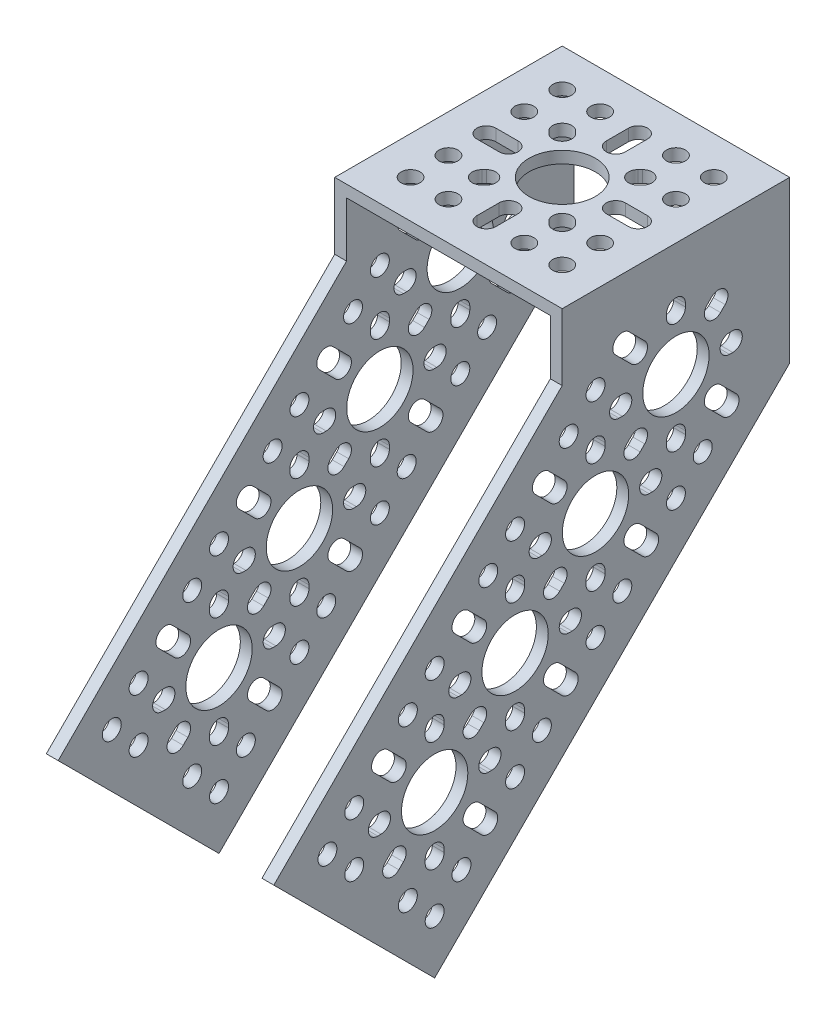
SolidWorks part; units mm, degrees
ref_plane "Front Plane" through (0, 0, 0) normal (0, 0, 1) x (1, 0, 0)
ref_plane "Top Plane" through (0, 0, 0) normal (0, 1, 0) x (1, 0, 0)
ref_plane "Right Plane" through (0, 0, 0) normal (1, 0, 0) x (0, 0, -1)
ref_plane "Plane1" through (21.5, 0, 0) normal (-1, 0, 0) x (0, -1, 0)
sketch "Sketch1" plane through (21.5, 0, 0) normal (-1, 0, 0) x (0, -1, 0)
  line L0 (45.5, -9.9411) -> (11.5589, 24)
  line L1 (11.5589, 24) -> (11.5589, -24)
  line L2 (11.5589, -24) -> (31.4411, -24)
  line L3 (31.4411, -24) -> (45.5, -9.9411)
extrude "Boss-Extrude1" add sketch "Sketch1" against normal blind 2.5
sketch "Sketch2" plane through (0, -11.5589, 0) normal (0, 1, 0) x (-1, 0, 0)
  line L0 (-24, 24) -> (-21.5, 24)
  line L1 (-21.5, 24) -> (-21.5, -24)
  line L2 (-21.5, -24) -> (-24, -24)
  line L3 (-24, -24) -> (-24, 24)
extrude "Boss-Extrude2" add sketch "Sketch2" along normal blind 11.5589
sketch "Sketch3" plane through (0, -17.7794, 17.7794) normal (0, -0.7071, 0.7071) x (1, 0, 0)
  line L0 (21.5, -39.2028) -> (21.5, 8.7972)
  line L1 (21.5, 8.7972) -> (24, 8.7972)
  line L2 (24, 8.7972) -> (24, -39.2028)
  line L3 (24, -39.2028) -> (21.5, -39.2028)
extrude "Boss-Extrude3" add sketch "Sketch3" along normal blind 86.0589
sketch "Sketch4" plane through (0, 0, 0) normal (0, 1, 0) x (-1, 0, 0)
  line L0 (21.5, -24) -> (-24, -24)
  line L1 (-24, -24) -> (-24, 24)
  line L2 (-24, 24) -> (21.5, 24)
  line L3 (21.5, 24) -> (21.5, -24)
extrude "Boss-Extrude4" add sketch "Sketch4" along normal blind 2.5
sketch "Sketch5" plane through (-21.5, 0, 0) normal (-1, 0, 0) x (0, 0, 1)
  line L0 (50.9117, -106.3528) -> (-24, -31.4411)
  line L1 (-24, -31.4411) -> (-24, 2.5)
  line L2 (-24, 2.5) -> (24, 2.5)
  line L3 (24, 2.5) -> (24, -11.5589)
  line L4 (24, -11.5589) -> (84.8528, -72.4117)
  line L5 (84.8528, -72.4117) -> (50.9117, -106.3528)
extrude "Boss-Extrude5" add sketch "Sketch5" along normal blind 2.5
sketch "Sketch6" plane through (-21.5, 0, 0) normal (1, 0, 0) x (0, 0, -1)
  line L0 (-63.6396, -62.5122) -> (-60.3259, -65.8259)
  line L1 (-57.4975, -62.9975) -> (-60.8112, -59.6838)
  arc A0 (-60.8112, -59.6838) -> (-63.6396, -62.5122) centre (-62.2254, -61.098) ccw
  arc A1 (-60.3259, -65.8259) -> (-57.4975, -62.9975) centre (-58.9117, -64.4117) ccw
extrude "Cut-Extrude1" cut sketch "Sketch6" against normal through all
sketch "Sketch7" plane through (-21.5, 0, 0) normal (1, 0, 0) x (0, 0, -1)
  line L0 (-44.3259, -81.8259) -> (-41.0122, -85.1396)
  line L1 (-38.1838, -82.3112) -> (-41.4975, -78.9975)
  arc A0 (-41.0122, -85.1396) -> (-38.1838, -82.3112) centre (-39.598, -83.7254) ccw
  arc A1 (-41.4975, -78.9975) -> (-44.3259, -81.8259) centre (-42.9117, -80.4117) ccw
extrude "Cut-Extrude2" cut sketch "Sketch7" against normal through all
sketch "Sketch8" plane through (-21.5, 0, 0) normal (1, 0, 0) x (0, 0, -1)
  line L0 (-46.669, -45.5416) -> (-43.3553, -48.8553)
  line L1 (-40.5269, -46.0269) -> (-43.8406, -42.7132)
  arc A0 (-43.8406, -42.7132) -> (-46.669, -45.5416) centre (-45.2548, -44.1274) ccw
  arc A1 (-43.3553, -48.8553) -> (-40.5269, -46.0269) centre (-41.9411, -47.4411) ccw
extrude "Cut-Extrude3" cut sketch "Sketch8" against normal through all
sketch "Sketch9" plane through (-21.5, 0, 0) normal (1, 0, 0) x (0, 0, -1)
  line L0 (-27.3553, -64.8553) -> (-24.0416, -68.169)
  line L1 (-21.2132, -65.3406) -> (-24.5269, -62.0269)
  arc A0 (-24.0416, -68.169) -> (-21.2132, -65.3406) centre (-22.6274, -66.7548) ccw
  arc A1 (-24.5269, -62.0269) -> (-27.3553, -64.8553) centre (-25.9411, -63.4411) ccw
extrude "Cut-Extrude4" cut sketch "Sketch9" against normal through all
sketch "Sketch10" plane through (-21.5, 0, 0) normal (1, 0, 0) x (0, 0, -1)
  line L0 (-29.6985, -28.5711) -> (-26.3848, -31.8848)
  line L1 (-23.5563, -29.0563) -> (-26.8701, -25.7426)
  arc A0 (-26.8701, -25.7426) -> (-29.6985, -28.5711) centre (-28.2843, -27.1569) ccw
  arc A1 (-26.3848, -31.8848) -> (-23.5563, -29.0563) centre (-24.9706, -30.4706) ccw
extrude "Cut-Extrude5" cut sketch "Sketch10" against normal through all
sketch "Sketch11" plane through (-21.5, 0, 0) normal (1, 0, 0) x (0, 0, -1)
  line L0 (-10.3848, -47.8848) -> (-7.0711, -51.1985)
  line L1 (-4.2426, -48.3701) -> (-7.5563, -45.0563)
  arc A0 (-7.0711, -51.1985) -> (-4.2426, -48.3701) centre (-5.6569, -49.7843) ccw
  arc A1 (-7.5563, -45.0563) -> (-10.3848, -47.8848) centre (-8.9706, -46.4706) ccw
extrude "Cut-Extrude6" cut sketch "Sketch11" against normal through all
sketch "Sketch12" plane through (-21.5, 0, 0) normal (1, 0, 0) x (0, 0, -1)
  line L0 (-12.7279, -11.6005) -> (-9.4142, -14.9142)
  line L1 (-6.5858, -12.0858) -> (-9.8995, -8.7721)
  arc A0 (-9.8995, -8.7721) -> (-12.7279, -11.6005) centre (-11.3137, -10.1863) ccw
  arc A1 (-9.4142, -14.9142) -> (-6.5858, -12.0858) centre (-8, -13.5) ccw
extrude "Cut-Extrude7" cut sketch "Sketch12" against normal through all
sketch "Sketch13" plane through (-21.5, 0, 0) normal (1, 0, 0) x (0, 0, -1)
  line L0 (6.5858, -30.9142) -> (9.8995, -34.2279)
  line L1 (12.7279, -31.3995) -> (9.4142, -28.0858)
  arc A0 (9.8995, -34.2279) -> (12.7279, -31.3995) centre (11.3137, -32.8137) ccw
  arc A1 (9.4142, -28.0858) -> (6.5858, -30.9142) centre (8, -29.5) ccw
extrude "Cut-Extrude8" cut sketch "Sketch13" against normal through all
sketch "Sketch14" plane through (-21.5, 0, 0) normal (1, 0, 0) x (0, 0, -1)
  line L0 (-58.468, -82.7965) -> (-57.4975, -81.8259)
  line L1 (-60.3259, -78.9975) -> (-61.2965, -79.968)
  arc A0 (-57.4975, -81.8259) -> (-60.3259, -78.9975) centre (-58.9117, -80.4117) ccw
  arc A1 (-61.2965, -79.968) -> (-58.468, -82.7965) centre (-59.8823, -81.3823) ccw
extrude "Cut-Extrude9" cut sketch "Sketch14" against normal through all
sketch "Sketch15" plane through (-21.5, 0, 0) normal (1, 0, 0) x (0, 0, -1)
  line L0 (-41.4975, -65.8259) -> (-40.5269, -64.8553)
  line L1 (-43.3553, -62.0269) -> (-44.3259, -62.9975)
  arc A0 (-40.5269, -64.8553) -> (-43.3553, -62.0269) centre (-41.9411, -63.4411) ccw
  arc A1 (-44.3259, -62.9975) -> (-41.4975, -65.8259) centre (-42.9117, -64.4117) ccw
extrude "Cut-Extrude10" cut sketch "Sketch15" against normal through all
sketch "Sketch16" plane through (-21.5, 0, 0) normal (1, 0, 0) x (0, 0, -1)
  line L0 (-24.5269, -48.8553) -> (-23.5563, -47.8848)
  line L1 (-26.3848, -45.0563) -> (-27.3553, -46.0269)
  arc A0 (-23.5563, -47.8848) -> (-26.3848, -45.0563) centre (-24.9706, -46.4706) ccw
  arc A1 (-27.3553, -46.0269) -> (-24.5269, -48.8553) centre (-25.9411, -47.4411) ccw
extrude "Cut-Extrude11" cut sketch "Sketch16" against normal through all
sketch "Sketch17" plane through (-21.5, 0, 0) normal (1, 0, 0) x (0, 0, -1)
  line L0 (-7.5563, -31.8848) -> (-6.5858, -30.9142)
  line L1 (-9.4142, -28.0858) -> (-10.3848, -29.0563)
  arc A0 (-6.5858, -30.9142) -> (-9.4142, -28.0858) centre (-8, -29.5) ccw
  arc A1 (-10.3848, -29.0563) -> (-7.5563, -31.8848) centre (-8.9706, -30.4706) ccw
extrude "Cut-Extrude12" cut sketch "Sketch17" against normal through all
sketch "Sketch18" plane through (-21.5, 0, 0) normal (1, 0, 0) x (0, 0, -1)
  line L0 (7.5563, -11.1152) -> (6.5858, -12.0858)
  line L1 (9.4142, -14.9142) -> (10.3848, -13.9437)
  arc A0 (6.5858, -12.0858) -> (9.4142, -14.9142) centre (8, -13.5) ccw
  arc A1 (10.3848, -13.9437) -> (7.5563, -11.1152) centre (8.9706, -12.5294) ccw
extrude "Cut-Extrude13" cut sketch "Sketch18" against normal through all
sketch "Sketch19" plane through (-21.5, 0, 0) normal (1, 0, 0) x (0, 0, -1)
  line L0 (-48.9117, -61.098) -> (-48.9117, -60.4117)
  line L1 (-52.9117, -60.4117) -> (-52.9117, -61.098)
  arc A0 (-48.9117, -60.4117) -> (-52.9117, -60.4117) centre (-50.9117, -60.4117) ccw
  arc A1 (-52.9117, -61.098) -> (-48.9117, -61.098) centre (-50.9117, -61.098) ccw
extrude "Cut-Extrude14" cut sketch "Sketch19" against normal through all
sketch "Sketch20" plane through (-21.5, 0, 0) normal (1, 0, 0) x (0, 0, -1)
  line L0 (-39.598, -74.4117) -> (-38.9117, -74.4117)
  line L1 (-38.9117, -70.4117) -> (-39.598, -70.4117)
  arc A0 (-38.9117, -74.4117) -> (-38.9117, -70.4117) centre (-38.9117, -72.4117) ccw
  arc A1 (-39.598, -70.4117) -> (-39.598, -74.4117) centre (-39.598, -72.4117) ccw
extrude "Cut-Extrude15" cut sketch "Sketch20" against normal through all
sketch "Sketch21" plane through (-21.5, 0, 0) normal (1, 0, 0) x (0, 0, -1)
  line L0 (-52.9117, -83.7254) -> (-52.9117, -84.4117)
  line L1 (-48.9117, -84.4117) -> (-48.9117, -83.7254)
  arc A0 (-52.9117, -84.4117) -> (-48.9117, -84.4117) centre (-50.9117, -84.4117) ccw
  arc A1 (-48.9117, -83.7254) -> (-52.9117, -83.7254) centre (-50.9117, -83.7254) ccw
extrude "Cut-Extrude16" cut sketch "Sketch21" against normal through all
sketch "Sketch22" plane through (-21.5, 0, 0) normal (1, 0, 0) x (0, 0, -1)
  line L0 (-62.9117, -74.4117) -> (-62.2254, -74.4117)
  line L1 (-62.2254, -70.4117) -> (-62.9117, -70.4117)
  arc A0 (-62.9117, -70.4117) -> (-62.9117, -74.4117) centre (-62.9117, -72.4117) ccw
  arc A1 (-62.2254, -74.4117) -> (-62.2254, -70.4117) centre (-62.2254, -72.4117) ccw
extrude "Cut-Extrude17" cut sketch "Sketch22" against normal through all
sketch "Sketch23" plane through (-21.5, 0, 0) normal (1, 0, 0) x (0, 0, -1)
  line L0 (-31.9411, -44.1274) -> (-31.9411, -43.4411)
  line L1 (-35.9411, -43.4411) -> (-35.9411, -44.1274)
  arc A0 (-31.9411, -43.4411) -> (-35.9411, -43.4411) centre (-33.9411, -43.4411) ccw
  arc A1 (-35.9411, -44.1274) -> (-31.9411, -44.1274) centre (-33.9411, -44.1274) ccw
extrude "Cut-Extrude18" cut sketch "Sketch23" against normal through all
sketch "Sketch24" plane through (-21.5, 0, 0) normal (1, 0, 0) x (0, 0, -1)
  line L0 (-22.6274, -57.4411) -> (-21.9411, -57.4411)
  line L1 (-21.9411, -53.4411) -> (-22.6274, -53.4411)
  arc A0 (-21.9411, -57.4411) -> (-21.9411, -53.4411) centre (-21.9411, -55.4411) ccw
  arc A1 (-22.6274, -53.4411) -> (-22.6274, -57.4411) centre (-22.6274, -55.4411) ccw
extrude "Cut-Extrude19" cut sketch "Sketch24" against normal through all
sketch "Sketch25" plane through (-21.5, 0, 0) normal (1, 0, 0) x (0, 0, -1)
  line L0 (-35.9411, -66.7548) -> (-35.9411, -67.4411)
  line L1 (-31.9411, -67.4411) -> (-31.9411, -66.7548)
  arc A0 (-35.9411, -67.4411) -> (-31.9411, -67.4411) centre (-33.9411, -67.4411) ccw
  arc A1 (-31.9411, -66.7548) -> (-35.9411, -66.7548) centre (-33.9411, -66.7548) ccw
extrude "Cut-Extrude20" cut sketch "Sketch25" against normal through all
sketch "Sketch26" plane through (-21.5, 0, 0) normal (1, 0, 0) x (0, 0, -1)
  line L0 (-45.9411, -57.4411) -> (-45.2548, -57.4411)
  line L1 (-45.2548, -53.4411) -> (-45.9411, -53.4411)
  arc A0 (-45.9411, -53.4411) -> (-45.9411, -57.4411) centre (-45.9411, -55.4411) ccw
  arc A1 (-45.2548, -57.4411) -> (-45.2548, -53.4411) centre (-45.2548, -55.4411) ccw
extrude "Cut-Extrude21" cut sketch "Sketch26" against normal through all
sketch "Sketch27" plane through (-21.5, 0, 0) normal (1, 0, 0) x (0, 0, -1)
  line L0 (-14.9706, -27.1569) -> (-14.9706, -26.4706)
  line L1 (-18.9706, -26.4706) -> (-18.9706, -27.1569)
  arc A0 (-14.9706, -26.4706) -> (-18.9706, -26.4706) centre (-16.9706, -26.4706) ccw
  arc A1 (-18.9706, -27.1569) -> (-14.9706, -27.1569) centre (-16.9706, -27.1569) ccw
extrude "Cut-Extrude22" cut sketch "Sketch27" against normal through all
sketch "Sketch28" plane through (-21.5, 0, 0) normal (1, 0, 0) x (0, 0, -1)
  line L0 (-5.6569, -40.4706) -> (-4.9706, -40.4706)
  line L1 (-4.9706, -36.4706) -> (-5.6569, -36.4706)
  arc A0 (-4.9706, -40.4706) -> (-4.9706, -36.4706) centre (-4.9706, -38.4706) ccw
  arc A1 (-5.6569, -36.4706) -> (-5.6569, -40.4706) centre (-5.6569, -38.4706) ccw
extrude "Cut-Extrude23" cut sketch "Sketch28" against normal through all
sketch "Sketch29" plane through (-21.5, 0, 0) normal (1, 0, 0) x (0, 0, -1)
  line L0 (-18.9706, -49.7843) -> (-18.9706, -50.4706)
  line L1 (-14.9706, -50.4706) -> (-14.9706, -49.7843)
  arc A0 (-18.9706, -50.4706) -> (-14.9706, -50.4706) centre (-16.9706, -50.4706) ccw
  arc A1 (-14.9706, -49.7843) -> (-18.9706, -49.7843) centre (-16.9706, -49.7843) ccw
extrude "Cut-Extrude24" cut sketch "Sketch29" against normal through all
sketch "Sketch30" plane through (-21.5, 0, 0) normal (1, 0, 0) x (0, 0, -1)
  line L0 (-28.9706, -40.4706) -> (-28.2843, -40.4706)
  line L1 (-28.2843, -36.4706) -> (-28.9706, -36.4706)
  arc A0 (-28.9706, -36.4706) -> (-28.9706, -40.4706) centre (-28.9706, -38.4706) ccw
  arc A1 (-28.2843, -40.4706) -> (-28.2843, -36.4706) centre (-28.2843, -38.4706) ccw
extrude "Cut-Extrude25" cut sketch "Sketch30" against normal through all
sketch "Sketch31" plane through (-21.5, 0, 0) normal (1, 0, 0) x (0, 0, -1)
  line L0 (2, -10.1863) -> (2, -9.5)
  line L1 (-2, -9.5) -> (-2, -10.1863)
  arc A0 (2, -9.5) -> (-2, -9.5) centre (0, -9.5) ccw
  arc A1 (-2, -10.1863) -> (2, -10.1863) centre (0, -10.1863) ccw
extrude "Cut-Extrude26" cut sketch "Sketch31" against normal through all
sketch "Sketch32" plane through (-21.5, 0, 0) normal (1, 0, 0) x (0, 0, -1)
  line L0 (11.3137, -23.5) -> (12, -23.5)
  line L1 (12, -19.5) -> (11.3137, -19.5)
  arc A0 (12, -23.5) -> (12, -19.5) centre (12, -21.5) ccw
  arc A1 (11.3137, -19.5) -> (11.3137, -23.5) centre (11.3137, -21.5) ccw
extrude "Cut-Extrude27" cut sketch "Sketch32" against normal through all
sketch "Sketch33" plane through (-21.5, 0, 0) normal (1, 0, 0) x (0, 0, -1)
  line L0 (-2, -32.8137) -> (-2, -33.5)
  line L1 (2, -33.5) -> (2, -32.8137)
  arc A0 (-2, -33.5) -> (2, -33.5) centre (0, -33.5) ccw
  arc A1 (2, -32.8137) -> (-2, -32.8137) centre (0, -32.8137) ccw
extrude "Cut-Extrude28" cut sketch "Sketch33" against normal through all
sketch "Sketch34" plane through (0, 2.5, 0) normal (0, 1, 0) x (-1, 0, 0)
  line L0 (-2, -11.3137) -> (-2, -16)
  line L1 (2, -16) -> (2, -11.3137)
  arc A0 (-2, -16) -> (2, -16) centre (0, -16) ccw
  arc A1 (2, -11.3137) -> (-2, -11.3137) centre (0, -11.3137) ccw
extrude "Cut-Extrude29" cut sketch "Sketch34" against normal through all
sketch "Sketch35" plane through (0, 2.5, 0) normal (0, 1, 0) x (-1, 0, 0)
  line L0 (11.3137, -2) -> (16, -2)
  line L1 (16, 2) -> (11.3137, 2)
  arc A0 (16, -2) -> (16, 2) centre (16, 0) ccw
  arc A1 (11.3137, 2) -> (11.3137, -2) centre (11.3137, 0) ccw
extrude "Cut-Extrude30" cut sketch "Sketch35" against normal through all
sketch "Sketch36" plane through (0, 2.5, 0) normal (0, 1, 0) x (-1, 0, 0)
  line L0 (2, 11.3137) -> (2, 16)
  line L1 (-2, 16) -> (-2, 11.3137)
  arc A0 (2, 16) -> (-2, 16) centre (0, 16) ccw
  arc A1 (-2, 11.3137) -> (2, 11.3137) centre (0, 11.3137) ccw
extrude "Cut-Extrude31" cut sketch "Sketch36" against normal through all
sketch "Sketch37" plane through (0, 2.5, 0) normal (0, 1, 0) x (-1, 0, 0)
  line L0 (-11.3137, 2) -> (-16, 2)
  line L1 (-16, -2) -> (-11.3137, -2)
  arc A0 (-16, 2) -> (-16, -2) centre (-16, 0) ccw
  arc A1 (-11.3137, -2) -> (-11.3137, 2) centre (-11.3137, 0) ccw
extrude "Cut-Extrude32" cut sketch "Sketch37" against normal through all
sketch "Sketch38" plane through (0, 2.5, 0) normal (0, 1, 0) x (-1, 0, 0)
  line L0 (-7.0711, -9.8995) -> (-6.5858, -9.4142)
  line L1 (-9.4142, -6.5858) -> (-9.8995, -7.0711)
  arc A0 (-9.8995, -7.0711) -> (-7.0711, -9.8995) centre (-8.4853, -8.4853) ccw
  arc A1 (-6.5858, -9.4142) -> (-9.4142, -6.5858) centre (-8, -8) ccw
extrude "Cut-Extrude33" cut sketch "Sketch38" against normal through all
sketch "Sketch39" plane through (0, 2.5, 0) normal (0, 1, 0) x (-1, 0, 0)
  line L0 (6.5858, -9.4142) -> (7.0711, -9.8995)
  line L1 (9.8995, -7.0711) -> (9.4142, -6.5858)
  arc A0 (7.0711, -9.8995) -> (9.8995, -7.0711) centre (8.4853, -8.4853) ccw
  arc A1 (9.4142, -6.5858) -> (6.5858, -9.4142) centre (8, -8) ccw
extrude "Cut-Extrude34" cut sketch "Sketch39" against normal through all
sketch "Sketch40" plane through (0, 2.5, 0) normal (0, 1, 0) x (-1, 0, 0)
  line L0 (9.4142, 6.5858) -> (9.8995, 7.0711)
  line L1 (7.0711, 9.8995) -> (6.5858, 9.4142)
  arc A0 (9.8995, 7.0711) -> (7.0711, 9.8995) centre (8.4853, 8.4853) ccw
  arc A1 (6.5858, 9.4142) -> (9.4142, 6.5858) centre (8, 8) ccw
extrude "Cut-Extrude35" cut sketch "Sketch40" against normal through all
sketch "Sketch41" plane through (24, 0, 0) normal (1, 0, 0) x (0, 0, -1)
  line L0 (-63.6396, -62.5122) -> (-60.3259, -65.8259)
  line L1 (-57.4975, -62.9975) -> (-60.8112, -59.6838)
  arc A0 (-60.8112, -59.6838) -> (-63.6396, -62.5122) centre (-62.2254, -61.098) ccw
  arc A1 (-60.3259, -65.8259) -> (-57.4975, -62.9975) centre (-58.9117, -64.4117) ccw
extrude "Cut-Extrude36" cut sketch "Sketch41" against normal up to next
sketch "Sketch42" plane through (24, 0, 0) normal (1, 0, 0) x (0, 0, -1)
  line L0 (-44.3259, -81.8259) -> (-41.0122, -85.1396)
  line L1 (-38.1838, -82.3112) -> (-41.4975, -78.9975)
  arc A0 (-41.0122, -85.1396) -> (-38.1838, -82.3112) centre (-39.598, -83.7254) ccw
  arc A1 (-41.4975, -78.9975) -> (-44.3259, -81.8259) centre (-42.9117, -80.4117) ccw
extrude "Cut-Extrude37" cut sketch "Sketch42" against normal up to next
sketch "Sketch43" plane through (24, 0, 0) normal (1, 0, 0) x (0, 0, -1)
  line L0 (-46.669, -45.5416) -> (-43.3553, -48.8553)
  line L1 (-40.5269, -46.0269) -> (-43.8406, -42.7132)
  arc A0 (-43.8406, -42.7132) -> (-46.669, -45.5416) centre (-45.2548, -44.1274) ccw
  arc A1 (-43.3553, -48.8553) -> (-40.5269, -46.0269) centre (-41.9411, -47.4411) ccw
extrude "Cut-Extrude38" cut sketch "Sketch43" against normal up to next
sketch "Sketch44" plane through (24, 0, 0) normal (1, 0, 0) x (0, 0, -1)
  line L0 (-27.3553, -64.8553) -> (-24.0416, -68.169)
  line L1 (-21.2132, -65.3406) -> (-24.5269, -62.0269)
  arc A0 (-24.0416, -68.169) -> (-21.2132, -65.3406) centre (-22.6274, -66.7548) ccw
  arc A1 (-24.5269, -62.0269) -> (-27.3553, -64.8553) centre (-25.9411, -63.4411) ccw
extrude "Cut-Extrude39" cut sketch "Sketch44" against normal up to next
sketch "Sketch45" plane through (24, 0, 0) normal (1, 0, 0) x (0, 0, -1)
  line L0 (-29.6985, -28.5711) -> (-26.3848, -31.8848)
  line L1 (-23.5563, -29.0563) -> (-26.8701, -25.7426)
  arc A0 (-26.8701, -25.7426) -> (-29.6985, -28.5711) centre (-28.2843, -27.1569) ccw
  arc A1 (-26.3848, -31.8848) -> (-23.5563, -29.0563) centre (-24.9706, -30.4706) ccw
extrude "Cut-Extrude40" cut sketch "Sketch45" against normal up to next
sketch "Sketch46" plane through (24, 0, 0) normal (1, 0, 0) x (0, 0, -1)
  line L0 (-10.3848, -47.8848) -> (-7.0711, -51.1985)
  line L1 (-4.2426, -48.3701) -> (-7.5563, -45.0563)
  arc A0 (-7.0711, -51.1985) -> (-4.2426, -48.3701) centre (-5.6569, -49.7843) ccw
  arc A1 (-7.5563, -45.0563) -> (-10.3848, -47.8848) centre (-8.9706, -46.4706) ccw
extrude "Cut-Extrude41" cut sketch "Sketch46" against normal up to next
sketch "Sketch47" plane through (24, 0, 0) normal (1, 0, 0) x (0, 0, -1)
  line L0 (-12.7279, -11.6005) -> (-9.4142, -14.9142)
  line L1 (-6.5858, -12.0858) -> (-9.8995, -8.7721)
  arc A0 (-9.8995, -8.7721) -> (-12.7279, -11.6005) centre (-11.3137, -10.1863) ccw
  arc A1 (-9.4142, -14.9142) -> (-6.5858, -12.0858) centre (-8, -13.5) ccw
extrude "Cut-Extrude42" cut sketch "Sketch47" against normal up to next
sketch "Sketch48" plane through (24, 0, 0) normal (1, 0, 0) x (0, 0, -1)
  line L0 (6.5858, -30.9142) -> (9.8995, -34.2279)
  line L1 (12.7279, -31.3995) -> (9.4142, -28.0858)
  arc A0 (9.8995, -34.2279) -> (12.7279, -31.3995) centre (11.3137, -32.8137) ccw
  arc A1 (9.4142, -28.0858) -> (6.5858, -30.9142) centre (8, -29.5) ccw
extrude "Cut-Extrude43" cut sketch "Sketch48" against normal up to next
sketch "Sketch49" plane through (24, 0, 0) normal (1, 0, 0) x (0, 0, -1)
  line L0 (-58.468, -82.7965) -> (-57.4975, -81.8259)
  line L1 (-60.3259, -78.9975) -> (-61.2965, -79.968)
  arc A0 (-57.4975, -81.8259) -> (-60.3259, -78.9975) centre (-58.9117, -80.4117) ccw
  arc A1 (-61.2965, -79.968) -> (-58.468, -82.7965) centre (-59.8823, -81.3823) ccw
extrude "Cut-Extrude44" cut sketch "Sketch49" against normal through all
sketch "Sketch50" plane through (24, 0, 0) normal (1, 0, 0) x (0, 0, -1)
  line L0 (-41.4975, -65.8259) -> (-40.5269, -64.8553)
  line L1 (-43.3553, -62.0269) -> (-44.3259, -62.9975)
  arc A0 (-40.5269, -64.8553) -> (-43.3553, -62.0269) centre (-41.9411, -63.4411) ccw
  arc A1 (-44.3259, -62.9975) -> (-41.4975, -65.8259) centre (-42.9117, -64.4117) ccw
extrude "Cut-Extrude45" cut sketch "Sketch50" against normal through all
sketch "Sketch51" plane through (24, 0, 0) normal (1, 0, 0) x (0, 0, -1)
  line L0 (-24.5269, -48.8553) -> (-23.5563, -47.8848)
  line L1 (-26.3848, -45.0563) -> (-27.3553, -46.0269)
  arc A0 (-23.5563, -47.8848) -> (-26.3848, -45.0563) centre (-24.9706, -46.4706) ccw
  arc A1 (-27.3553, -46.0269) -> (-24.5269, -48.8553) centre (-25.9411, -47.4411) ccw
extrude "Cut-Extrude46" cut sketch "Sketch51" against normal through all
sketch "Sketch52" plane through (24, 0, 0) normal (1, 0, 0) x (0, 0, -1)
  line L0 (-7.5563, -31.8848) -> (-6.5858, -30.9142)
  line L1 (-9.4142, -28.0858) -> (-10.3848, -29.0563)
  arc A0 (-6.5858, -30.9142) -> (-9.4142, -28.0858) centre (-8, -29.5) ccw
  arc A1 (-10.3848, -29.0563) -> (-7.5563, -31.8848) centre (-8.9706, -30.4706) ccw
extrude "Cut-Extrude47" cut sketch "Sketch52" against normal through all
sketch "Sketch53" plane through (24, 0, 0) normal (1, 0, 0) x (0, 0, -1)
  line L0 (7.5563, -11.1152) -> (6.5858, -12.0858)
  line L1 (9.4142, -14.9142) -> (10.3848, -13.9437)
  arc A0 (6.5858, -12.0858) -> (9.4142, -14.9142) centre (8, -13.5) ccw
  arc A1 (10.3848, -13.9437) -> (7.5563, -11.1152) centre (8.9706, -12.5294) ccw
extrude "Cut-Extrude48" cut sketch "Sketch53" against normal through all
sketch "Sketch54" plane through (24, 0, 0) normal (1, 0, 0) x (0, 0, -1)
  line L0 (-48.9117, -61.098) -> (-48.9117, -60.4117)
  line L1 (-52.9117, -60.4117) -> (-52.9117, -61.098)
  arc A0 (-48.9117, -60.4117) -> (-52.9117, -60.4117) centre (-50.9117, -60.4117) ccw
  arc A1 (-52.9117, -61.098) -> (-48.9117, -61.098) centre (-50.9117, -61.098) ccw
extrude "Cut-Extrude49" cut sketch "Sketch54" against normal through all
sketch "Sketch55" plane through (24, 0, 0) normal (1, 0, 0) x (0, 0, -1)
  line L0 (-39.598, -74.4117) -> (-38.9117, -74.4117)
  line L1 (-38.9117, -70.4117) -> (-39.598, -70.4117)
  arc A0 (-38.9117, -74.4117) -> (-38.9117, -70.4117) centre (-38.9117, -72.4117) ccw
  arc A1 (-39.598, -70.4117) -> (-39.598, -74.4117) centre (-39.598, -72.4117) ccw
extrude "Cut-Extrude50" cut sketch "Sketch55" against normal through all
sketch "Sketch56" plane through (24, 0, 0) normal (1, 0, 0) x (0, 0, -1)
  line L0 (-52.9117, -83.7254) -> (-52.9117, -84.4117)
  line L1 (-48.9117, -84.4117) -> (-48.9117, -83.7254)
  arc A0 (-52.9117, -84.4117) -> (-48.9117, -84.4117) centre (-50.9117, -84.4117) ccw
  arc A1 (-48.9117, -83.7254) -> (-52.9117, -83.7254) centre (-50.9117, -83.7254) ccw
extrude "Cut-Extrude51" cut sketch "Sketch56" against normal through all
sketch "Sketch57" plane through (24, 0, 0) normal (1, 0, 0) x (0, 0, -1)
  line L0 (-62.2254, -70.4117) -> (-62.9117, -70.4117)
  line L1 (-62.9117, -74.4117) -> (-62.2254, -74.4117)
  arc A0 (-62.9117, -70.4117) -> (-62.9117, -74.4117) centre (-62.9117, -72.4117) ccw
  arc A1 (-62.2254, -74.4117) -> (-62.2254, -70.4117) centre (-62.2254, -72.4117) ccw
extrude "Cut-Extrude52" cut sketch "Sketch57" against normal through all
sketch "Sketch58" plane through (24, 0, 0) normal (1, 0, 0) x (0, 0, -1)
  line L0 (-31.9411, -44.1274) -> (-31.9411, -43.4411)
  line L1 (-35.9411, -43.4411) -> (-35.9411, -44.1274)
  arc A0 (-31.9411, -43.4411) -> (-35.9411, -43.4411) centre (-33.9411, -43.4411) ccw
  arc A1 (-35.9411, -44.1274) -> (-31.9411, -44.1274) centre (-33.9411, -44.1274) ccw
extrude "Cut-Extrude53" cut sketch "Sketch58" against normal through all
sketch "Sketch59" plane through (24, 0, 0) normal (1, 0, 0) x (0, 0, -1)
  line L0 (-22.6274, -57.4411) -> (-21.9411, -57.4411)
  line L1 (-21.9411, -53.4411) -> (-22.6274, -53.4411)
  arc A0 (-21.9411, -57.4411) -> (-21.9411, -53.4411) centre (-21.9411, -55.4411) ccw
  arc A1 (-22.6274, -53.4411) -> (-22.6274, -57.4411) centre (-22.6274, -55.4411) ccw
extrude "Cut-Extrude54" cut sketch "Sketch59" against normal through all
sketch "Sketch60" plane through (24, 0, 0) normal (1, 0, 0) x (0, 0, -1)
  line L0 (-35.9411, -66.7548) -> (-35.9411, -67.4411)
  line L1 (-31.9411, -67.4411) -> (-31.9411, -66.7548)
  arc A0 (-35.9411, -67.4411) -> (-31.9411, -67.4411) centre (-33.9411, -67.4411) ccw
  arc A1 (-31.9411, -66.7548) -> (-35.9411, -66.7548) centre (-33.9411, -66.7548) ccw
extrude "Cut-Extrude55" cut sketch "Sketch60" against normal through all
sketch "Sketch61" plane through (24, 0, 0) normal (1, 0, 0) x (0, 0, -1)
  line L0 (-45.2548, -53.4411) -> (-45.9411, -53.4411)
  line L1 (-45.9411, -57.4411) -> (-45.2548, -57.4411)
  arc A0 (-45.9411, -53.4411) -> (-45.9411, -57.4411) centre (-45.9411, -55.4411) ccw
  arc A1 (-45.2548, -57.4411) -> (-45.2548, -53.4411) centre (-45.2548, -55.4411) ccw
extrude "Cut-Extrude56" cut sketch "Sketch61" against normal through all
sketch "Sketch62" plane through (24, 0, 0) normal (1, 0, 0) x (0, 0, -1)
  line L0 (-14.9706, -27.1569) -> (-14.9706, -26.4706)
  line L1 (-18.9706, -26.4706) -> (-18.9706, -27.1569)
  arc A0 (-14.9706, -26.4706) -> (-18.9706, -26.4706) centre (-16.9706, -26.4706) ccw
  arc A1 (-18.9706, -27.1569) -> (-14.9706, -27.1569) centre (-16.9706, -27.1569) ccw
extrude "Cut-Extrude57" cut sketch "Sketch62" against normal through all
sketch "Sketch63" plane through (24, 0, 0) normal (1, 0, 0) x (0, 0, -1)
  line L0 (-5.6569, -40.4706) -> (-4.9706, -40.4706)
  line L1 (-4.9706, -36.4706) -> (-5.6569, -36.4706)
  arc A0 (-4.9706, -40.4706) -> (-4.9706, -36.4706) centre (-4.9706, -38.4706) ccw
  arc A1 (-5.6569, -36.4706) -> (-5.6569, -40.4706) centre (-5.6569, -38.4706) ccw
extrude "Cut-Extrude58" cut sketch "Sketch63" against normal through all
sketch "Sketch64" plane through (24, 0, 0) normal (1, 0, 0) x (0, 0, -1)
  line L0 (-18.9706, -49.7843) -> (-18.9706, -50.4706)
  line L1 (-14.9706, -50.4706) -> (-14.9706, -49.7843)
  arc A0 (-18.9706, -50.4706) -> (-14.9706, -50.4706) centre (-16.9706, -50.4706) ccw
  arc A1 (-14.9706, -49.7843) -> (-18.9706, -49.7843) centre (-16.9706, -49.7843) ccw
extrude "Cut-Extrude59" cut sketch "Sketch64" against normal through all
sketch "Sketch65" plane through (24, 0, 0) normal (1, 0, 0) x (0, 0, -1)
  line L0 (-28.2843, -36.4706) -> (-28.9706, -36.4706)
  line L1 (-28.9706, -40.4706) -> (-28.2843, -40.4706)
  arc A0 (-28.9706, -36.4706) -> (-28.9706, -40.4706) centre (-28.9706, -38.4706) ccw
  arc A1 (-28.2843, -40.4706) -> (-28.2843, -36.4706) centre (-28.2843, -38.4706) ccw
extrude "Cut-Extrude60" cut sketch "Sketch65" against normal through all
sketch "Sketch66" plane through (24, 0, 0) normal (1, 0, 0) x (0, 0, -1)
  line L0 (2, -10.1863) -> (2, -9.5)
  line L1 (-2, -9.5) -> (-2, -10.1863)
  arc A0 (2, -9.5) -> (-2, -9.5) centre (0, -9.5) ccw
  arc A1 (-2, -10.1863) -> (2, -10.1863) centre (0, -10.1863) ccw
extrude "Cut-Extrude61" cut sketch "Sketch66" against normal through all
sketch "Sketch67" plane through (24, 0, 0) normal (1, 0, 0) x (0, 0, -1)
  line L0 (11.3137, -23.5) -> (12, -23.5)
  line L1 (12, -19.5) -> (11.3137, -19.5)
  arc A0 (12, -23.5) -> (12, -19.5) centre (12, -21.5) ccw
  arc A1 (11.3137, -19.5) -> (11.3137, -23.5) centre (11.3137, -21.5) ccw
extrude "Cut-Extrude62" cut sketch "Sketch67" against normal through all
sketch "Sketch68" plane through (24, 0, 0) normal (1, 0, 0) x (0, 0, -1)
  line L0 (-2, -32.8137) -> (-2, -33.5)
  line L1 (2, -33.5) -> (2, -32.8137)
  arc A0 (-2, -33.5) -> (2, -33.5) centre (0, -33.5) ccw
  arc A1 (2, -32.8137) -> (-2, -32.8137) centre (0, -32.8137) ccw
extrude "Cut-Extrude63" cut sketch "Sketch68" against normal through all
sketch "Sketch69" plane through (24, 0, 0) normal (1, 0, 0) x (0, 0, -1)
  line L0 (-11.3137, -19.5) -> (-12, -19.5)
  line L1 (-12, -23.5) -> (-11.3137, -23.5)
  arc A0 (-12, -19.5) -> (-12, -23.5) centre (-12, -21.5) ccw
  arc A1 (-11.3137, -23.5) -> (-11.3137, -19.5) centre (-11.3137, -21.5) ccw
extrude "Cut-Extrude64" cut sketch "Sketch69" against normal up to next
sketch "Sketch70" plane through (0, 2.5, 0) normal (0, 1, 0) x (-1, 0, 0)
  line L0 (-6.5858, 9.4142) -> (-7.0711, 9.8995)
  line L1 (-9.8995, 7.0711) -> (-9.4142, 6.5858)
  arc A0 (-7.0711, 9.8995) -> (-9.8995, 7.0711) centre (-8.4853, 8.4853) ccw
  arc A1 (-9.4142, 6.5858) -> (-6.5858, 9.4142) centre (-8, 8) ccw
extrude "Cut-Extrude65" cut sketch "Sketch70" against normal through all
sketch "Sketch71" plane through (-24, 0, 0) normal (-1, 0, 0) x (0, 0, 1)
  line L0 (12, -19.5) -> (11.3137, -19.5)
  line L1 (11.3137, -23.5) -> (12, -23.5)
  arc A0 (12, -23.5) -> (12, -19.5) centre (12, -21.5) ccw
  arc A1 (11.3137, -19.5) -> (11.3137, -23.5) centre (11.3137, -21.5) ccw
extrude "Cut-Extrude66" cut sketch "Sketch71" against normal through all
hole_wizard "Hole1" positions "Sketch73" profile "Sketch72" legacy
sketch "Sketch73" plane through (-21.5, 0, 0) normal (1, 0, 0) x (0, 0, -1)
  point P0 (0, -21.5)
  point P1 (-16.9706, -38.4706)
  point P2 (-33.9411, -55.4411)
  point P3 (-50.9117, -72.4117)
sketch "Sketch72" plane through (-21.5, -21.5, 0) normal (0, 1, 0) x (0, 0, -1)
  line L0 (0, 0) -> (0, 2.5)
  line L1 (0, 2.5) -> (7, 2.5)
  line L2 (7, 2.5) -> (7, 0)
  line L3 (7, 0) -> (0, 0)
  line L4 (0, 110) -> (0, -10) construction
  dimension "Diameter" = 14
  dimension "Depth" = 2.5
hole_wizard "Hole2" positions "Sketch75" profile "Sketch74" legacy
sketch "Sketch75" plane through (-21.5, 0, 0) normal (1, 0, 0) x (0, 0, -1)
  point P0 (-50.9117, -49.7843)
  point P1 (-39.598, -38.4706)
  point P2 (-33.9411, -32.8137)
  point P3 (-22.6274, -21.5)
  point P4 (-16.9706, -15.8431)
  point P5 (0, -44.1274)
  point P6 (5.6569, -38.4706)
  point P7 (-11.3137, -55.4411)
  point P8 (-16.9706, -61.098)
  point P9 (-56.5685, -55.4411)
  point P10 (-67.8823, -78.0685)
  point P11 (-73.5391, -72.4117)
  point P12 (-67.8823, -66.7548)
  point P13 (-28.2843, -72.4117)
  point P14 (-33.9411, -78.0685)
  point P15 (-45.2548, -89.3823)
  point P16 (-50.9117, -95.0391)
  point P17 (-56.5685, -89.3823)
sketch "Sketch74" plane through (-21.5, -49.7843, 50.9117) normal (0, 1, 0) x (0, 0, -1)
  line L0 (0, 0) -> (0, 2.5)
  line L1 (0, 2.5) -> (2, 2.5)
  line L2 (2, 2.5) -> (2, 0)
  line L3 (2, 0) -> (0, 0)
  line L4 (0, 110) -> (0, -10) construction
  dimension "Diameter" = 4
  dimension "Depth" = 2.5
hole_wizard "Hole3" positions "Sketch77" profile "Sketch76" legacy
sketch "Sketch77" plane through (0, 2.5, 0) normal (0, 1, 0) x (1, 0, 0)
  point P0 (0, 0)
sketch "Sketch76" plane through (0, 2.5, 0) normal (1, 0, 0) x (0, 0, 1)
  line L0 (0, 0) -> (0, 108.8528)
  line L1 (0, 108.8528) -> (7, 108.8528)
  line L2 (7, 108.8528) -> (7, 0)
  line L3 (7, 0) -> (0, 0)
  line L4 (0, 110) -> (0, -10) construction
  dimension "Diameter" = 14
  dimension "Depth" = 108.8528
hole_wizard "Hole4" positions "Sketch79" profile "Sketch78" legacy
sketch "Sketch79" plane through (0, 2.5, 0) normal (0, 1, 0) x (1, 0, 0)
  point P0 (8, 16)
  point P1 (16, 16)
  point P2 (16, 8)
  point P3 (16, -8)
  point P4 (16, -16)
  point P5 (8, -16)
  point P6 (-8, -16)
  point P7 (-16, -16)
  point P8 (-16, -8)
  point P9 (-16, 8)
  point P10 (-16, 16)
  point P11 (-8, 16)
sketch "Sketch78" plane through (8, 2.5, -16) normal (1, 0, 0) x (0, 0, 1)
  line L0 (0, 0) -> (0, 108.8528)
  line L1 (0, 108.8528) -> (2, 108.8528)
  line L2 (2, 108.8528) -> (2, 0)
  line L3 (2, 0) -> (0, 0)
  line L4 (0, 110) -> (0, -10) construction
  dimension "Diameter" = 4
  dimension "Depth" = 108.8528
hole_wizard "Hole5" positions "Sketch81" profile "Sketch80" legacy
sketch "Sketch81" plane through (24, 0, 0) normal (1, 0, 0) x (0, 0, -1)
  point P0 (0, -21.5)
  point P1 (-16.9706, -38.4706)
  point P2 (-33.9411, -55.4411)
  point P3 (-50.9117, -72.4117)
sketch "Sketch80" plane through (24, -21.5, 0) normal (0, 1, 0) x (0, 0, -1)
  line L0 (0, 0) -> (0, 48)
  line L1 (0, 48) -> (7, 48)
  line L2 (7, 48) -> (7, 0)
  line L3 (7, 0) -> (0, 0)
  line L4 (0, 110) -> (0, -10) construction
  dimension "Diameter" = 14
  dimension "Depth" = 48
hole_wizard "Hole6" positions "Sketch83" profile "Sketch82" legacy
sketch "Sketch83" plane through (24, 0, 0) normal (1, 0, 0) x (0, 0, -1)
  point P0 (-50.9117, -49.7843)
  point P1 (-39.598, -38.4706)
  point P2 (-33.9411, -32.8137)
  point P3 (-22.6274, -21.5)
  point P4 (-16.9706, -15.8431)
  point P5 (0, -44.1274)
  point P6 (5.6569, -38.4706)
  point P7 (-11.3137, -55.4411)
  point P8 (-16.9706, -61.098)
  point P9 (-56.5685, -55.4411)
  point P10 (-67.8823, -78.0685)
  point P11 (-73.5391, -72.4117)
  point P12 (-67.8823, -66.7548)
  point P13 (-28.2843, -72.4117)
  point P14 (-33.9411, -78.0685)
  point P15 (-45.2548, -89.3823)
  point P16 (-50.9117, -95.0391)
  point P17 (-56.5685, -89.3823)
sketch "Sketch82" plane through (24, -49.7843, 50.9117) normal (0, 1, 0) x (0, 0, -1)
  line L0 (0, 0) -> (0, 48)
  line L1 (0, 48) -> (2, 48)
  line L2 (2, 48) -> (2, 0)
  line L3 (2, 0) -> (0, 0)
  line L4 (0, 110) -> (0, -10) construction
  dimension "Diameter" = 4
  dimension "Depth" = 48
